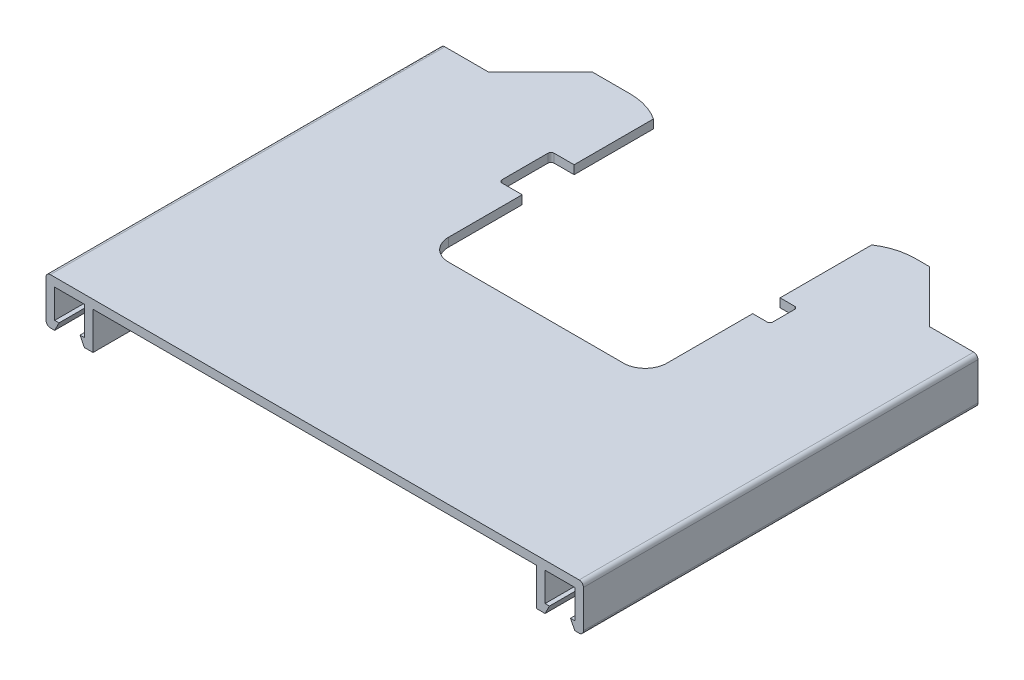
SolidWorks part; units mm, degrees
ref_plane "Front Plane" through (0, 0, 0) normal (0, 0, 1) x (1, 0, 0)
ref_plane "Top Plane" through (0, 0, 0) normal (0, 1, 0) x (1, 0, 0)
ref_plane "Right Plane" through (0, 0, 0) normal (1, 0, 0) x (0, 0, -1)
sketch "Sketch1" plane through (0, 0, 0) normal (0, 1, 0) x (1, 0, 0)
  line L1 (0, 0) -> (186.3, 0)
  line L2 (0, 0) -> (0, 72.76)
  line L3 (0, 72.76) -> (186.3, 72.76)
  line L4 (186.3, 0) -> (186.3, 72.76)
  dimension "D1" = 186.3
  dimension "D2" = 72.76
extrude "Boss-Extrude1" add sketch "Sketch1" along normal blind 3
sketch "Sketch3" plane through (0, 3, 0) normal (0, 1, 0) x (1, 0, 0)
  line L1 (0, 72.76) -> (59.3, 72.76)
  line L2 (0, 72.76) -> (0, 136.76)
  line L3 (0, 136.76) -> (59.3, 136.76)
  line L4 (59.3, 72.76) -> (59.3, 136.76)
  line L5 (186.3, 72.76) -> (134.95, 72.76)
  line L6 (186.3, 72.76) -> (186.3, 136.76)
  line L7 (186.3, 136.76) -> (134.95, 136.76)
  line L8 (134.95, 72.76) -> (134.95, 136.76)
  dimension "D1" = 59.3
  dimension "D2" = 64
  dimension "D3" = 51.35
extrude "Boss-Extrude3" add sketch "Sketch3" against normal up to vertex (3 mm away) up to point (0, 0, -72.76)
sketch "Sketch5" plane through (0, 3, 0) normal (0, 1, 0) x (1, 0, 0)
  line L0 (169.56, 136.76) -> (151.56, 154.76)
  line L1 (186.3, 136.76) -> (134.95, 136.76) construction
  line L2 (151.56, 154.76) -> (146.56, 154.76)
  line L3 (134.95, 151.26) -> (134.95, 136.76)
  line L4 (186.3, 0) -> (186.3, 136.76) construction
  line L5 (134.95, 136.76) -> (169.56, 136.76)
  line L6 (97.125, 72.76) -> (97.125, 169.1741) construction
  line L7 (134.95, 72.76) -> (59.3, 72.76) construction
  line L8 (59.3, 136.76) -> (16.69, 136.76)
  line L9 (59.3, 151.26) -> (59.3, 136.76)
  line L10 (34.69, 154.76) -> (47.69, 154.76)
  line L11 (16.69, 136.76) -> (34.69, 154.76)
  line L12 (59.3, 136.76) -> (0, 136.76) construction
  arc A0 (134.95, 151.26) -> (146.56, 154.76) centre (146.56, 133.754) cw
  arc A1 (59.3, 151.26) -> (47.69, 154.76) centre (47.69, 133.754) ccw
  point P21 (23.7617, 136.76)
  dimension "D5" = 5
  dimension "D1" = 45
  dimension "D2" = 18
  dimension "D3" = 16.74
  dimension "D4" = 14.5
  dimension "D6" = 45
  dimension "D7" = 13
extrude "Boss-Extrude4" add sketch "Sketch5" against normal up to vertex (3 mm away) up to point (186.3, 0, -136.76)
sketch "Sketch6" plane through (0, 3, 0) normal (0, 1, 0) x (1, 0, 0)
  line L0 (59.3, 72.76) -> (59.3, 151.26) construction
  line L1 (59.3, 123.76) -> (52.3, 123.76)
  line L2 (59.3, 123.76) -> (59.3, 105.76)
  line L3 (59.3, 105.76) -> (52.3, 105.76)
  line L4 (51.3, 122.76) -> (51.3, 106.76)
  line L5 (134.95, 114.76) -> (59.3, 114.76) construction
  line L6 (134.95, 151.26) -> (134.95, 72.76) construction
  line L8 (134.95, 72.76) -> (59.3, 72.76) construction
  line L9 (139.95, 110.01) -> (134.95, 110.01)
  line L10 (140.95, 111.01) -> (140.95, 118.51)
  line L11 (134.95, 110.01) -> (134.95, 119.51)
  line L12 (139.95, 119.51) -> (134.95, 119.51)
  line L13 (140.95, 110.01) -> (134.95, 119.51) construction
  line L14 (134.95, 110.01) -> (140.95, 119.51) construction
  arc A0 (52.3, 105.76) -> (51.3, 106.76) centre (52.3, 106.76) cw
  arc A1 (52.3, 123.76) -> (51.3, 122.76) centre (52.3, 122.76) ccw
  arc A2 (140.95, 111.01) -> (139.95, 110.01) centre (139.95, 111.01) cw
  arc A3 (140.95, 118.51) -> (139.95, 119.51) centre (139.95, 118.51) ccw
  point P8 (0, 0)
  point P10 (137.95, 114.76)
  point P11 (0, 0)
  point P15 (51.3, 105.76)
  point P18 (51.3, 123.76)
  point P23 (151.7338, 119.51)
  point P24 (0, 0)
  dimension "D4" = 1
  dimension "D7" = 1
  dimension "D1" = 18
  dimension "D2" = 42
  dimension "D3" = 8
  dimension "D5" = 6
  dimension "D6" = 9.5
extrude "Cut-Extrude1" cut sketch "Sketch6" against normal blind 10
sketch "Sketch9" plane through (0, 0, 0) normal (0, -1, 0) x (1, 0, 0)
  line L0 (16.69, -136.76) -> (0, -136.76) construction
  line L1 (0, 0) -> (3, 0)
  line L2 (0, 0) -> (0, -136.76)
  line L3 (0, -136.76) -> (3, -136.76)
  line L4 (3, 0) -> (3, -136.76)
  line L5 (0, 0) -> (186.3, 0) construction
  line L6 (186.3, -136.76) -> (183.3, -136.76)
  line L7 (186.3, -136.76) -> (186.3, 0)
  line L8 (186.3, 0) -> (183.3, 0)
  line L9 (183.3, -136.76) -> (183.3, 0)
  line L10 (186.3, -136.76) -> (169.56, -136.76) construction
  line L11 (13.3, 0) -> (16.3, 0)
  line L12 (13.3, 0) -> (13.3, -136.76)
  line L13 (13.3, -136.76) -> (16.3, -136.76)
  line L14 (16.3, 0) -> (16.3, -136.76)
  line L15 (173, -136.76) -> (170, -136.76)
  line L16 (173, -136.76) -> (173, 0)
  line L17 (173, 0) -> (170, 0)
  line L18 (170, -136.76) -> (170, 0)
  point P24 (170, -0.7598)
  point P25 (170, 0)
  dimension "D1" = 3
  dimension "D2" = 10.3
  dimension "D3" = 10.3
extrude "Boss-Extrude7" add sketch "Sketch9" along normal blind 13
fillet "Fillet1" radius 7.5 2 edges at (134.95, 1.5, -72.76) (59.3, 1.5, -72.76)
sketch "Sketch10" plane through (0, 0, -136.76) normal (0, 0, -1) x (-1, 0, 0)
  line L0 (-183.3, -13) -> (-181.8, -10)
  line L1 (-181.8, -10) -> (-183.3, -10)
  line L2 (-183.3, -13) -> (-183.3, 0) construction
  line L3 (-183.3, -10) -> (-183.3, -13)
  line L4 (-178.15, 0) -> (-178.15, -13) construction
  line L5 (-183.3, 0) -> (-173, 0) construction
  line L6 (-174.5, -10) -> (-173, -10)
  line L7 (-173, -13) -> (-174.5, -10)
  line L8 (-173, -10) -> (-173, -13)
  line L9 (-13.3, 0) -> (-3, 0) construction
  line L11 (-8.15, 0) -> (-8.15, -13.0787) construction
  line L12 (-13.3, -10) -> (-13.3, -13)
  line L13 (-13.3, -13) -> (-11.8, -10)
  line L14 (-11.8, -10) -> (-13.3, -10)
  line L19 (-13.3, -13) -> (-13.3, 0) construction
  line L20 (-4.5, -10) -> (-3, -10)
  line L21 (-3, -13) -> (-4.5, -10)
  line L22 (-3, -10) -> (-3, -13)
  point P13 (-8.15, 0)
  point P15 (-92.4337, 0)
  point P25 (-13.3, -10)
  point P28 (-13.3, -13)
  point P30 (-12.2029, -11.0229)
  dimension "D1" = 3
  dimension "D2" = 1.5
extrude "Boss-Extrude8" add sketch "Sketch10" against normal up to vertex (136.76 mm away) up to point (186.3, 3, 0)
fillet "Fillet2" radius 1.5 4 edges at (0, 3, -68.38) (186.3, 3, -68.38) (0, -13, -68.38) (186.3, -13, -68.38)
